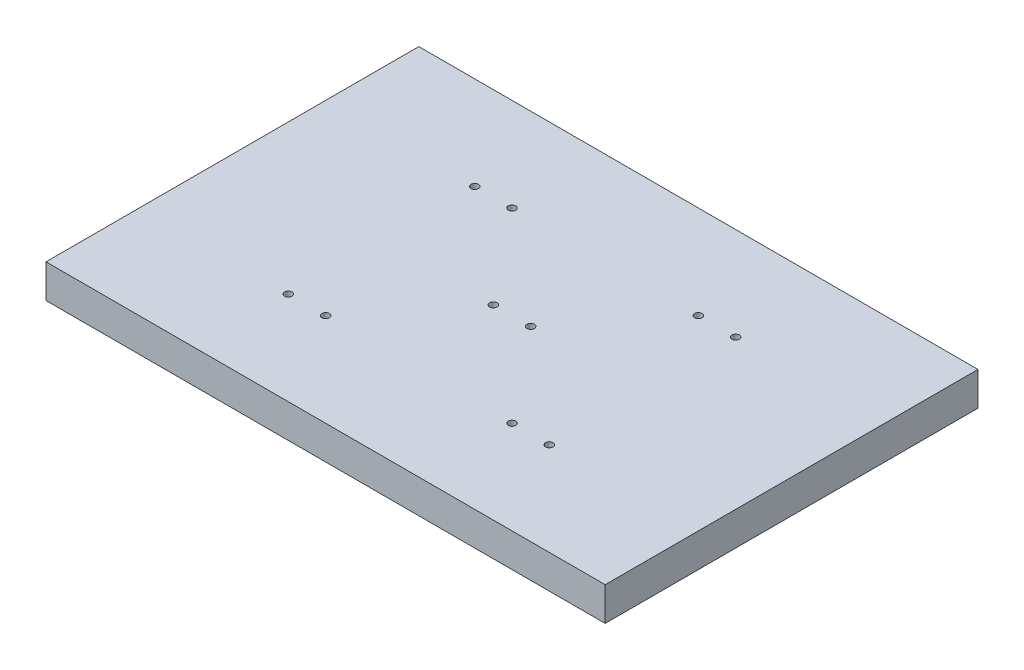
SolidWorks part; units mm, degrees
ref_plane "Front Plane" through (0, 0, 0) normal (0, 0, 1) x (1, 0, 0)
ref_plane "Top Plane" through (0, 0, 0) normal (0, 1, 0) x (1, 0, 0)
ref_plane "Right Plane" through (0, 0, 0) normal (1, 0, 0) x (0, 0, -1)
sketch "Sketch1" plane through (0, 0, 0) normal (0, 1, 0) x (1, 0, 0)
  line L0 (0, -1723.1449) -> (0, 84434.0997) construction
  line L1 (-1723.1449, 0) -> (84434.0997, 0) construction
  line L2 (-1723.1449, -50) -> (84434.0997, -50) construction
  line L3 (-150, 100) -> (150, 100)
  line L4 (-150, 100) -> (-150, -100)
  line L5 (-150, -100) -> (150, -100)
  line L6 (150, 100) -> (150, -100)
  line L7 (-1723.1449, 50) -> (84434.0997, 50) construction
  line L8 (60, -1723.1449) -> (60, 84434.0997) construction
  line L9 (-60, -1723.1449) -> (-60, 84434.0997) construction
  circle A0 centre (10, 0) radius 2
  circle A1 centre (-10, 0) radius 2
  circle A2 centre (70, 50) radius 2
  circle A3 centre (50, 50) radius 2
  circle A4 centre (-70, 50) radius 2
  circle A5 centre (-50, 50) radius 2
  circle A6 centre (-50, -50) radius 2
  circle A7 centre (-70, -50) radius 2
  circle A8 centre (50, -50) radius 2
  circle A9 centre (70, -50) radius 2
  point P4 (0, 0)
  point P10 (0, 100)
  point P11 (-150, 0)
  dimension "D3" = 4
  dimension "D9" = 4
  dimension "D1" = 200
  dimension "D2" = 300
  dimension "D4" = 10
  dimension "D10" = 10
  dimension "D5" = 50
  dimension "D6" = 50
  dimension "D7" = 60
  dimension "D8" = 60
extrude "Boss-Extrude1" add sketch "Sketch1" along normal blind 18
